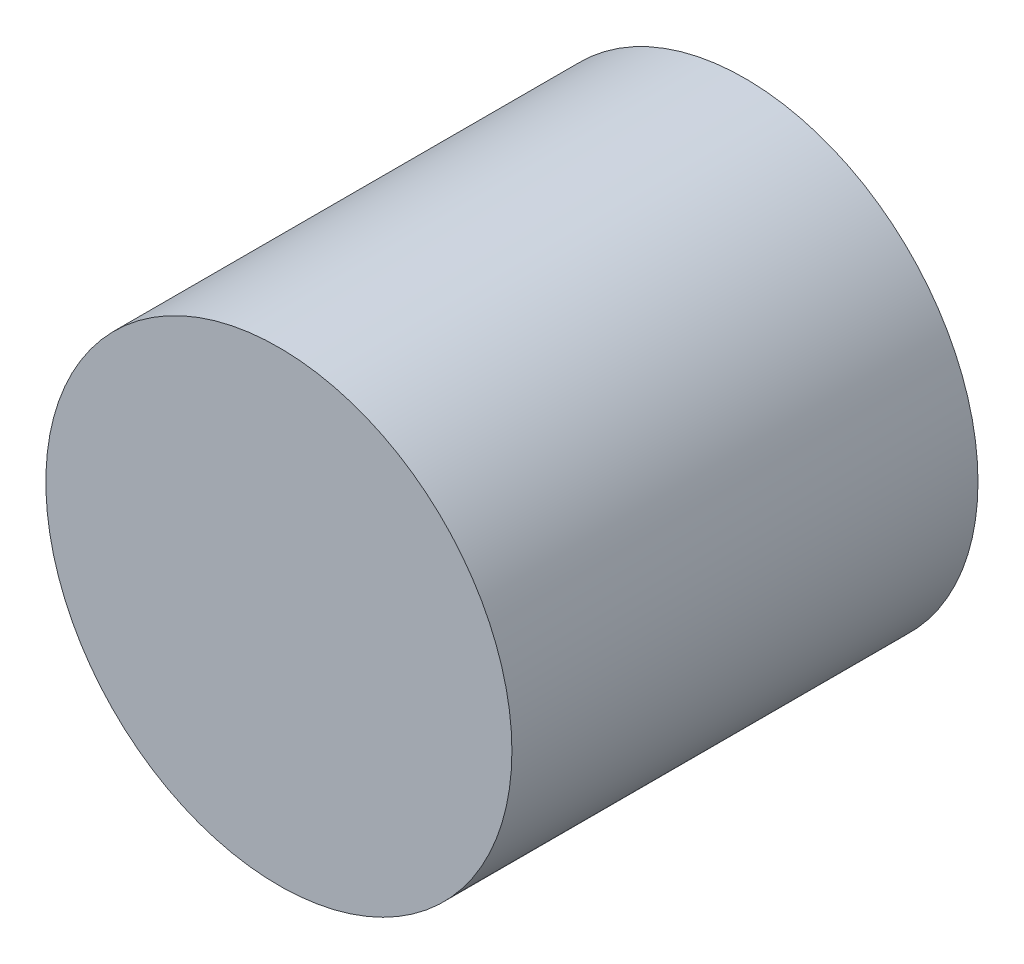
SolidWorks part; units mm, degrees
ref_plane "Piano frontale" through (0, 0, 0) normal (0, 0, 1) x (1, 0, 0)
ref_plane "Piano superiore" through (0, 0, 0) normal (0, 1, 0) x (1, 0, 0)
ref_plane "Piano destro" through (0, 0, 0) normal (1, 0, 0) x (0, 0, -1)
sketch "Schizzo1" plane through (0, 0, 0) normal (0, 0, 1) x (1, 0, 0)
  circle A0 centre (0, 0) radius 60
  dimension "D1" = 120
extrude "Estrusione-Estrusione1" add sketch "Schizzo1" along normal blind 120
